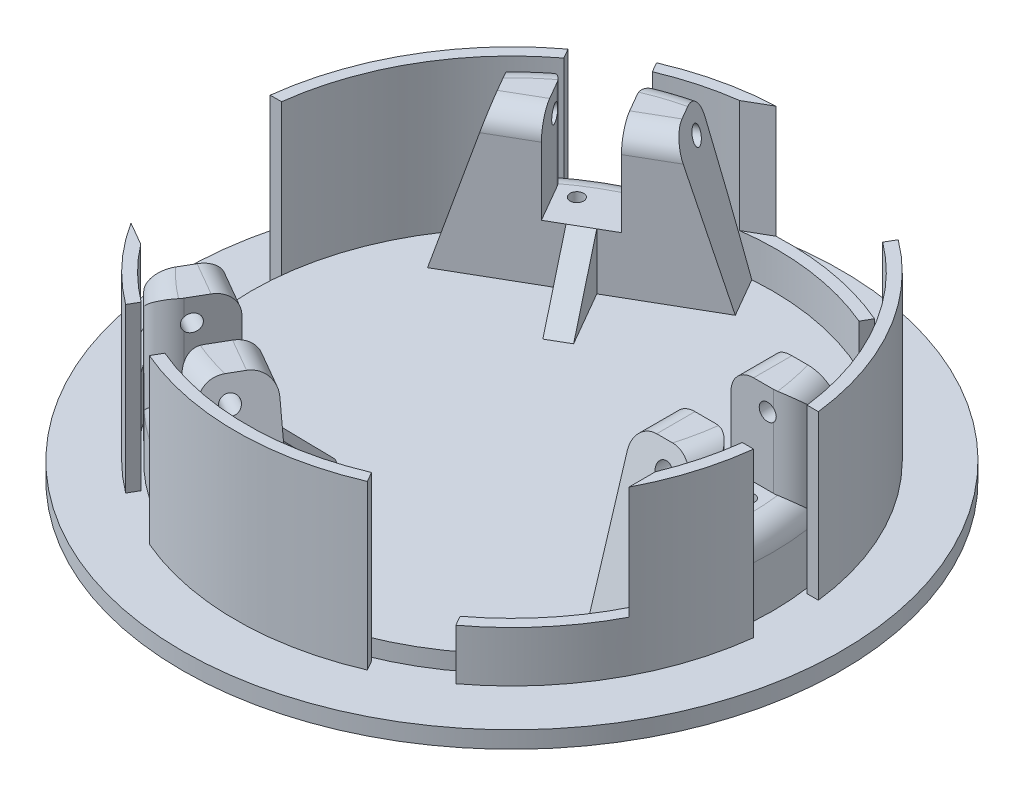
SolidWorks part; units mm, degrees
ref_plane "Front Plane" through (0, 0, 0) normal (0, 0, 1) x (1, 0, 0)
ref_plane "Top Plane" through (0, 0, 0) normal (0, 1, 0) x (1, 0, 0)
ref_plane "Right Plane" through (0, 0, 0) normal (1, 0, 0) x (0, 0, -1)
sketch "Sketch2" plane through (0, 0, 0) normal (0, 0, 1) x (1, 0, 0)
  line L0 (0, 0) -> (15, 0)
  line L1 (15, 0) -> (15, 14.5)
  line L2 (15, 14.5) -> (11, 14.5)
  line L3 (11, 14.5) -> (11, 1.5)
  line L4 (11, 1.5) -> (0, 1.5)
  line L5 (0, 1.5) -> (0, 0)
  dimension "D1" = 15
  dimension "D2" = 14.5
  dimension "D3" = 4
  dimension "D4" = 1.5
extrude "Boss-Extrude1" add sketch "Sketch2" along normal blind 20
ref_plane "Plane2" through (0, 0, 10) normal (0, 0, 1) x (1, 0, 0)
sketch "Sketch9" plane through (0, 1.5, 0) normal (0, 1, 0) x (1, 0, 0)
  line L0 (5.5, -20) -> (0, -12.5)
  line L1 (11, -20) -> (0, -20) construction
  line L2 (0, -20) -> (0, 0) construction
  line L3 (0, -12.5) -> (0, -7.5)
  line L4 (0, -7.5) -> (5.5, 0)
  line L5 (11, 0) -> (0, 0) construction
  line L6 (5.5, 0) -> (0, 0)
  line L7 (0, 0) -> (0, -20)
  line L8 (0, -20) -> (5.5, -20)
  point P14 (0, -10)
  point P15 (0, -10)
  line M3 (11, 0) -> (0, 0)
  line M4 (0, 0) -> (0, -20)
  line M5 (0, -20) -> (11, -20)
  dimension "D3" = 5
extrude "Cut-Extrude6" cut sketch "Sketch9" against normal through all contours L4 M4 M3 | L0 M5 M4 region at (1.8333, 1.5, 17.5) region at (1.8333, 1.5, 2.5)
sketch "Sketch10" plane through (11, 0, 0) normal (-1, 0, 0) x (0, 0, 1)
  line L0 (0, 1.5) -> (0, 14.5)
  line L1 (0, 14.5) -> (20, 14.5)
  line L2 (20, 14.5) -> (20, 1.5)
  line L3 (20, 1.5) -> (16, 14.5)
  line L4 (16, 14.5) -> (4, 14.5)
  line L5 (4, 14.5) -> (0, 1.5)
  line L6 (0, 1.5) -> (0.1757, 1.9576)
  line L7 (20, 14.5) -> (0, 14.5) construction
  line L8 (7.4, 14.5) -> (7.4, 6.5)
  line L9 (7.4, 6.5) -> (12.6, 6.5)
  line L10 (12.6, 6.5) -> (12.6, 14.5)
  point P4 (10, 6.5)
  point P13 (10, 14.5)
  point P14 (10, 14.5)
  line M1 (0, 14.5) -> (0, 1.5)
  line M3 (20, 1.5) -> (20, 14.5)
  line M4 (20, 14.5) -> (0, 14.5)
  dimension "D1" = 6
  dimension "D2" = 5.2
  dimension "D3" = 8
extrude "Cut-Extrude8" cut sketch "Sketch10" against normal through all contours L5 M4 M1 | L9 L10 L4 L8 | L3 M3 M4 region at (11, 10.1667, 18.6667) region at (11, 10.5, 10) region at (11, 10.1667, 1.3333)
sketch "Sketch12" plane through (0, 0, 10) normal (0, 0, 1) x (1, 0, 0)
  line L0 (5.377, 1.5) -> (11, 6.5)
  line L1 (5.5, 1.5) -> (0, 1.5) construction
  line L2 (11, 6.5) -> (11, 1.5)
  line L3 (11, 1.5) -> (5.377, 1.5)
extrude "Boss-Extrude3" add sketch "Sketch12" along normal mid plane 2
sketch "Sketch13" plane through (0, 0, 0) normal (0, 1, 0) x (1, 0, 0)
  line L0 (15, -20) -> (15, 0)
  arc A0 (15, 0) -> (15, -20) centre (-5.851, -10) cw
  dimension "D1" = 23.125
extrude "Boss-Extrude4" add sketch "Sketch13" along normal up to surface (14.5 mm away) up to face at (13, 14.5, 5.7)
sketch "Sketch14" plane through (15, 0, 0) normal (-1, 0, 0) x (0, 0, 1)
  line L0 (16, 14.5) -> (20, 1.5)
  line L1 (20, 1.5) -> (20, 14.5)
  line L2 (20, 14.5) -> (16, 14.5)
  line L3 (4, 14.5) -> (0, 14.5)
  line L4 (0, 14.5) -> (0, 1.5)
  line L5 (0, 1.5) -> (4, 14.5)
  line L7 (7.4, 14.5) -> (12.6, 14.5)
  line L8 (7.4, 14.5) -> (7.4, 6.5)
  line L9 (7.4, 6.5) -> (12.6, 6.5)
  line L10 (12.6, 14.5) -> (12.6, 6.5)
extrude "Cut-Extrude10" cut sketch "Sketch14" against normal through all
sketch "Sketch15" plane through (0, 6.5, 0) normal (0, 1, 0) x (1, 0, 0)
  line L0 (11, -9) -> (11, 0) construction
  line L1 (17.1273, -7.4) -> (11, -7.4) construction
  circle A0 centre (14, -8.9) radius 0.6
  dimension "D1" = 1.2
  dimension "D2" = 3
  dimension "D3" = 1.5
extrude "Cut-Extrude11" cut sketch "Sketch15" against normal blind 25
fillet "Fillet1" radius 2 7 edges at (16.8684, 14.5, 5.6879) (16.8684, 14.5, 14.3121) (11, 14.5, 14.3) (11, 14.5, 5.7) (17.1273, 10.5, 7.4) (17.1273, 10.5, 12.6) (17.274, 6.5, 10)
sketch "Sketch11" plane through (0, 0, 7.4) normal (0, 0, 1) x (1, 0, 0)
  line L0 (14.404, 14.5) -> (13, 14.5) construction
  line L1 (11, 1.5) -> (11, 12.5) construction
  circle A0 centre (14.25, 12.5) radius 0.75
  dimension "D1" = 1.5
  dimension "D2" = 2
  dimension "D3" = 3.25
extrude "Cut-Extrude9" cut sketch "Sketch11" against normal through all both and the other way through all
sketch "Sketch16" plane through (0, 0, 0) normal (0, 1, 0) x (1, 0, 0)
  line L0 (0, -12.5) -> (0, -7.5) construction
  line L33 (-5.851, 13.125) -> (-5.851, -33.125) construction
  circle A0 centre (-5.851, -10) radius 23.125
  circle A2 centre (-5.851, -10) radius 29.2554
  arc A5 (16.7191, -15.0355) -> (16.7191, -4.9645) centre (-5.851, -10) ccw construction
  point P7 (0, -10)
  dimension "D1" = 46.25
extrude "Boss-Extrude5" add sketch "Sketch16" against normal blind 1.5
sketch "Sketch22" plane through (0, -1.5, 0) normal (0, -1, 0) x (-1, 0, 0)
  circle A0 centre (5.851, -10) radius 23.125
  dimension "D1" = 46.25
extrude "Boss-Extrude9" add sketch "Sketch22" against normal up to surface (1.5 mm away) up to face at (14, 0, 9.5)
sketch "Sketch23" plane through (0, 1.5, 0) normal (0, 1, 0) x (1, 0, 0)
  circle A0 centre (-5.851, -10) radius 23.125
  arc A3 (-26.7021, 0) -> (15, -20) centre (-5.851, -10) ccw construction
  dimension "D1" = 46.25
pattern_circular "CirPattern5" count 3 over 360 about axis through (-5.851, 0, 10) along (0, 1, 0) of "Boss-Extrude1", "Cut-Extrude6", "Cut-Extrude8", "Boss-Extrude3", "Boss-Extrude4", "Cut-Extrude10", "Cut-Extrude11", "Fillet1", "Cut-Extrude9"
sketch "Sketch24" plane through (0, -1.5, 0) normal (0, -1, 0) x (1, 0, 0)
  circle A0 centre (-5.851, 10) radius 23.125
  dimension "D1" = 46.25
extrude "Boss-Extrude10" add sketch "Sketch24" against normal up to surface (3 mm away) up to face at (6.5754, 1.5, 10)
sketch "Sketch25" plane through (0, -1.5, 0) normal (0, 1, 0) x (1, 0, 0)
  circle A0 centre (-5.851, -10) radius 23.5
  circle A1 centre (-5.851, -10) radius 24.5
  dimension "D1" = 47
  dimension "D2" = 49
extrude "Boss-Extrude11" add sketch "Sketch25" along normal up to surface (16 mm away) up to face at (-19.2474, 14.5, -5.2685)
sketch "Sketch26" plane through (0, 14.5, 0) normal (0, 1, 0) x (1, 0, 0)
  line L0 (29.0151, -7.125) -> (29.0151, -12.875)
  line L2 (11, -11) -> (11, -9) construction
  line L3 (11, -10) -> (29.0151, -10) construction
  line L4 (29.0151, -7.125) -> (17.3964, -7.125)
  line L5 (17.3964, -7.125) -> (17.3964, -12.875)
  line L6 (17.3964, -12.875) -> (29.0151, -12.875)
  dimension "D1" = 5.75
extrude "Cut-Extrude12" cut sketch "Sketch26" against normal up to surface (14.5 mm away) up to face at (-5.851, 0, 34.5)
pattern_circular "CirPattern6" count 6 over 360 about axis through (-5.851, 0, 10) along (0, 1, 0) of "Cut-Extrude12"
sketch "Sketch27" plane through (0, 14.5, 0) normal (0, 1, 0) x (1, 0, 0)
  line L0 (15.8675, -18.9752) -> (15.8675, -21.3382)
  line L2 (8.3005, -28.7612) -> (8.8042, -29.6335)
  line L3 (18.4797, -12.875) -> (17.4724, -12.875)
  line L4 (8.3005, -28.7612) -> (8.8042, -29.6335)
  arc A2 (8.3005, -28.7612) -> (17.4724, -12.875) centre (-5.851, -10) ccw
  arc A3 (8.8042, -29.6335) -> (18.4797, -12.875) centre (-5.851, -10) ccw
  arc A4 (8.3005, -28.7612) -> (15.8675, -18.9752) centre (-5.851, -10) ccw
  arc A5 (8.8042, -29.6335) -> (15.8675, -21.3382) centre (-5.851, -10) ccw
  dimension "D1" = 0
extrude "Cut-Extrude13" cut sketch "Sketch27" against normal blind 10
pattern_circular "CirPattern7" count 3 over 360 about axis through (-5.851, 0, 10) along (0, 1, 0) of "Cut-Extrude13"
